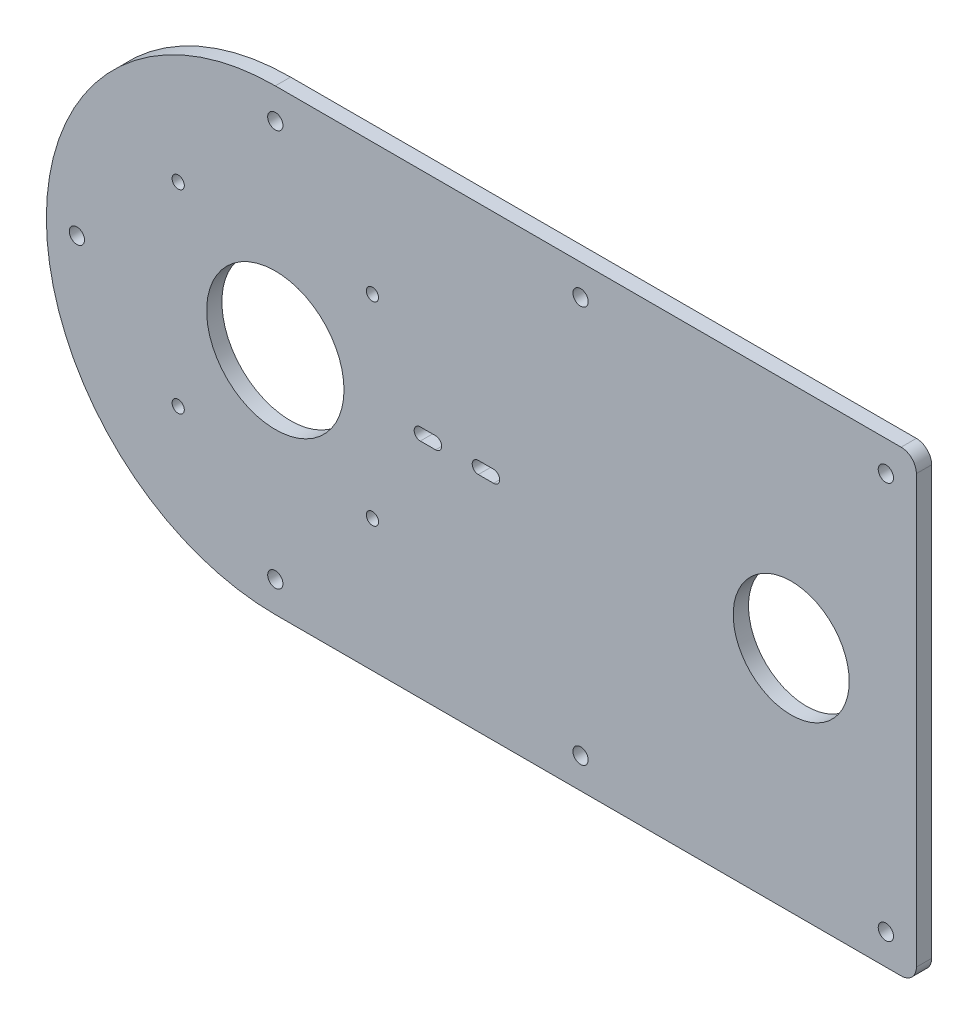
SolidWorks part; units mm, degrees
ref_plane "Front Plane" through (0, 0, 0) normal (0, 0, 1) x (1, 0, 0)
ref_plane "Top Plane" through (0, 0, 0) normal (0, 1, 0) x (1, 0, 0)
ref_plane "Right Plane" through (0, 0, 0) normal (1, 0, 0) x (0, 0, -1)
sketch "Sketch1" plane through (0, 0, 0) normal (0, 0, 1) x (1, 0, 0)
  line L1 (30.0007, 92.5455) -> (235.0007, 92.5455)
  line L3 (30.0007, -57.4545) -> (235.0007, -57.4545)
  line L4 (240.0007, 87.5455) -> (240.0007, -52.4545)
  line L5 (77.5007, 19.5455) -> (82.5007, 19.5455)
  line L6 (77.5007, 15.5455) -> (82.5007, 15.5455)
  line L7 (101.5007, 19.5455) -> (96.5007, 19.5455)
  line L8 (101.5007, 15.5455) -> (96.5007, 15.5455)
  arc A0 (235.0007, -57.4545) -> (240.0007, -52.4545) centre (235.0007, -52.4545) ccw
  arc A1 (235.0007, 92.5455) -> (240.0007, 87.5455) centre (235.0007, 87.5455) cw
  arc A2 (30.0007, 92.5455) -> (30.0007, -57.4545) centre (30.0007, 17.5455) ccw
  circle A7 centre (-34.9993, 17.5455) radius 2.5
  circle A10 centre (30.0007, -47.4545) radius 2.5
  circle A11 centre (30.0007, 82.5455) radius 2.5
  circle A12 centre (230.0007, -47.4545) radius 2.5
  circle A13 centre (230.0007, 82.5455) radius 2.5
  circle A15 centre (130.0007, 82.5455) radius 2.5
  circle A16 centre (130.0007, -47.4545) radius 2.5
  circle A17 centre (199.0007, 17.5455) radius 19
  circle A18 centre (30.0007, 17.5455) radius 22.5
  arc A19 (77.5007, 19.5455) -> (77.5007, 15.5455) centre (77.5007, 17.5455) ccw
  arc A20 (82.5007, 15.5455) -> (82.5007, 19.5455) centre (82.5007, 17.5455) ccw
  arc A21 (101.5007, 15.5455) -> (101.5007, 19.5455) centre (101.5007, 17.5455) ccw
  arc A22 (96.5007, 19.5455) -> (96.5007, 15.5455) centre (96.5007, 17.5455) ccw
  circle A23 centre (61.8157, 49.3605) radius 2
  circle A24 centre (61.8157, -14.2695) radius 2
  circle A25 centre (-1.8143, -14.2695) radius 2
  circle A26 centre (-1.8143, 49.3605) radius 2
  point P2 (30.0007, 17.5455)
  point P14 (30.0007, 17.5455)
  point P21 (-34.9993, 17.5455)
  point P43 (-1.8143, 48.5427)
  point P44 (-2.6633, -13.4071)
  point P49 (30.0007, 17.5455)
  dimension "D1" = 5
  dimension "D2" = 38
  dimension "D3" = 45
  dimension "D4" = 5
  dimension "D5" = 5
  dimension "D6" = 5
  dimension "D7" = 5
  dimension "D8" = 5
  dimension "D9" = 5
  dimension "D10" = 5
  dimension "D11" = 4
  dimension "D12" = 4
  dimension "D13" = 4
  dimension "D14" = 4
extrude "Boss-Extrude1" add sketch "Sketch1" along normal blind 5
